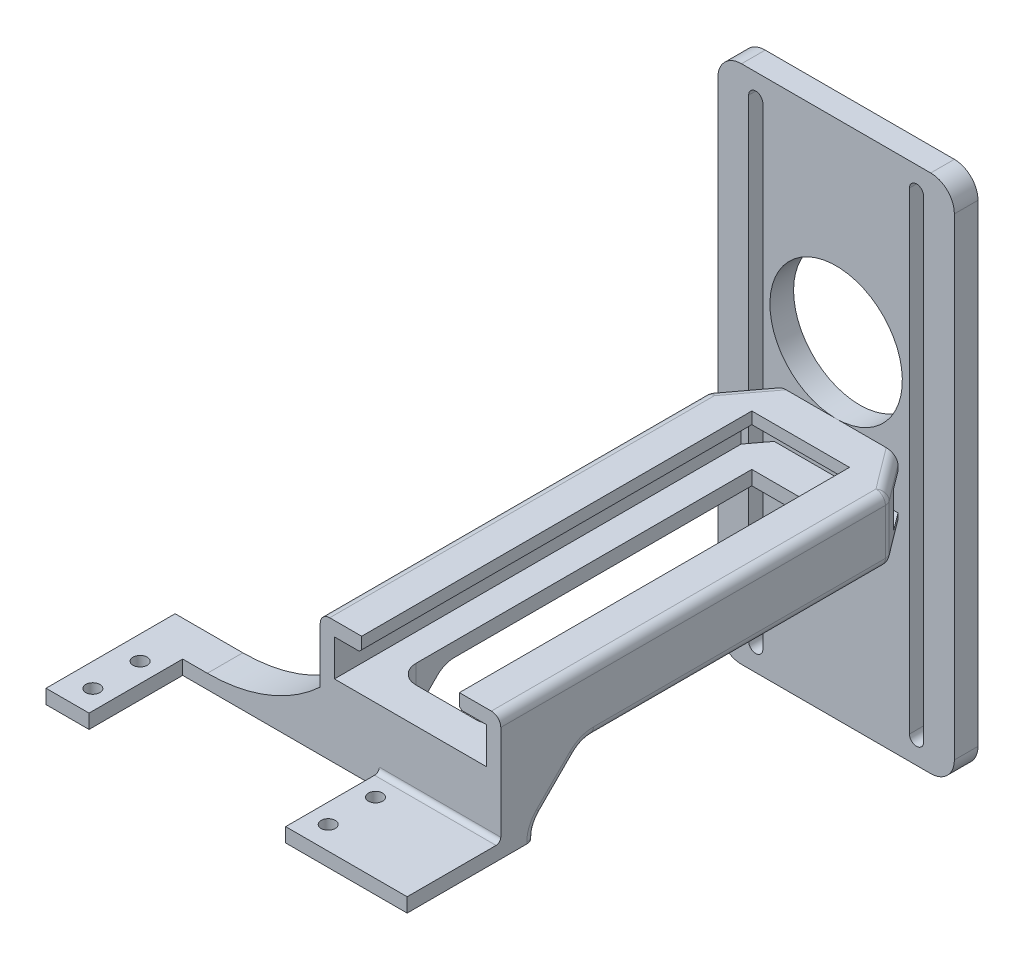
SolidWorks part; units mm, degrees
ref_plane "Front Plane" through (0, 0, 0) normal (0, 0, 1) x (1, 0, 0)
ref_plane "Top Plane" through (0, 0, 0) normal (0, 1, 0) x (1, 0, 0)
ref_plane "Right Plane" through (0, 0, 0) normal (1, 0, 0) x (0, 0, -1)
sketch "Sketch1" plane through (0, 0, 0) normal (0, 0, 1) x (1, 0, 0)
  line L0 (-69.7691, 23.4512) -> (-75.5286, 23.4512)
  line L1 (-75.5286, 23.4512) -> (-75.5286, 15.7512)
  line L2 (-75.5286, 15.7512) -> (-69.7691, 15.7512)
  line L3 (-69.7691, 15.7512) -> (-69.7691, 12.7512)
  line L4 (-69.7691, 12.7512) -> (-78.5286, 12.7512)
  line L5 (-78.5286, 12.7512) -> (-78.5286, 26.4512)
  line L6 (-78.5286, 26.4512) -> (-69.7691, 26.4512)
  line L7 (-69.7691, 26.4512) -> (-69.7691, 23.4512)
  line L8 (-49.1122, 23.4512) -> (-49.1122, 26.4512)
  line L9 (-49.1122, 26.4512) -> (-40.3527, 26.4512)
  line L10 (-40.3527, 26.4512) -> (-40.3527, 12.7512)
  line L11 (-40.3527, 12.7512) -> (-49.1122, 12.7512)
  line L12 (-49.1122, 12.7512) -> (-49.1122, 15.7512)
  line L13 (-49.1122, 15.7512) -> (-43.3527, 15.7512)
  line L14 (-43.3527, 15.7512) -> (-43.3527, 23.4512)
  line L15 (-43.3527, 23.4512) -> (-49.1122, 23.4512)
  dimension "D2" = 5.7594
  dimension "D8" = 3
  dimension "D9" = 3
extrude "Boss-Extrude1" add sketch "Sketch1" along normal blind 55 and the other way blind 35
sketch "Sketch2" plane through (0, 26.4512, 0) normal (0, 1, 0) x (1, 0, 0)
  line L0 (-40.3527, 35) -> (-40.3527, -55) construction
  line L6 (-78.5286, 35) -> (-40.3527, 35)
  line L7 (-78.5286, 35) -> (-78.5286, 27.5)
  line L8 (-78.5286, 27.5) -> (-40.3527, 27.5)
  line L9 (-40.3527, 35) -> (-40.3527, 27.5)
  dimension "D1" = 7.5
extrude "Boss-Extrude2" add sketch "Sketch2" against normal up to vertex (3 mm away) up to point (-69.7691, 23.4512, -35)
sketch "Sketch3" plane through (0, 12.7512, 0) normal (0, -1, 0) x (1, 0, 0)
  line L0 (-40.3527, -35) -> (-40.3527, 55) construction
  line L1 (-78.5286, 55) -> (-40.3527, 55)
  line L2 (-78.5286, 55) -> (-78.5286, 47.5)
  line L3 (-78.5286, 47.5) -> (-40.3527, 47.5)
  line L4 (-40.3527, 55) -> (-40.3527, 47.5)
  line L6 (-78.5286, -35) -> (-40.3527, -35)
  line L7 (-78.5286, -35) -> (-78.5286, -27.5)
  line L8 (-78.5286, -27.5) -> (-40.3527, -27.5)
  line L9 (-40.3527, -35) -> (-40.3527, -27.5)
  line L10 (-69.7691, -27.5) -> (-49.1122, -27.5) construction
extrude "Boss-Extrude3" add sketch "Sketch3" against normal up to vertex (3 mm away) up to point (-69.7691, 15.7512, 55)
ref_plane "MidSlide" through (0, 19.6012, 0) normal (0, 1, 0) x (1, 0, 0)
ref_plane "Plane2" through (-59.4407, 0, 0) normal (1, 0, 0) x (0, 0, -1)
sketch "Sketch4" plane through (0, 3.3512, 0) normal (0, -1, 0) x (1, 0, 0)
  line L0 (-69.7691, 47.5) -> (-49.1122, 47.5) construction
  line L1 (-116.7182, 74.8) -> (-116.7182, 47.5)
  line L2 (-116.7182, 47.5) -> (-40.3527, 47.5)
  line L3 (-40.3527, -35) -> (-40.3527, 55) construction
  line L4 (-40.3527, 47.5) -> (-40.3527, 55)
  line L5 (-113.1286, 73.8) -> (-107.1286, 73.8) construction
  line L6 (-116.7182, 74.8) -> (-107.6165, 74.8)
  line L7 (-107.6165, 74.8) -> (-107.6165, 55)
  line L8 (-40.3527, 55) -> (-107.6165, 55) construction
  line L9 (-107.1165, 73.8) -> (-107.1165, 56) construction
  line L11 (-78.5286, 55) -> (-40.3527, 55) construction
  line L12 (-107.6165, 55) -> (-66.0407, 55)
  line L13 (-66.0407, 55) -> (-66.0407, 74.8)
  line L14 (-66.0407, 74.8) -> (-40.3527, 74.8)
  line L15 (-40.3527, 74.8) -> (-40.3527, 55)
  line L16 (-66.5407, 56) -> (-66.5407, 73.8) construction
  arc A0 (-113.5286, 68.65) -> (-113.5286, 71.15) centre (-111.7182, 69.9) ccw construction
  circle A1 centre (-111.7182, 69.9) radius 1.5
  circle A2 centre (-111.7182, 59.9) radius 1.5
  circle A3 centre (-61.939, 69.9) radius 1.5
  circle A4 centre (-61.939, 59.9) radius 1.5
  circle A5 centre (-64.4407, 35.969) radius 1.5 construction
  dimension "D1" = 5
  dimension "D2" = 1
  dimension "D3" = 0.5
  dimension "D4" = 0.5
extrude "Boss-Extrude4" add sketch "Sketch4" along normal blind 3 separate body
sketch "Sketch5" plane through (0, 12.7512, 0) normal (0, -1, 0) x (1, 0, 0)
  line L0 (-116.7182, 47.5) -> (-40.3527, 47.5) construction
  line L1 (-78.5355, 47.5) -> (-40.3527, 47.5)
  line L2 (-78.5355, 47.5) -> (-78.5355, 55)
  line L3 (-78.5355, 55) -> (-40.3527, 55)
  line L4 (-40.3527, 47.5) -> (-40.3527, 55)
  line L5 (-40.3527, 47.5) -> (-40.3527, 74.8) construction
extrude "Boss-Extrude5" add sketch "Sketch5" along normal up to next
fillet "Fillet1" radius 35 1 edges
sketch "Sketch6" plane through (0, 0, -35) normal (0, 0, -1) x (-1, 0, 0)
  line L0 (75.5286, 23.4512) -> (43.3527, 23.4512) construction
  line L1 (34.4407, 81.4512) -> (84.4407, 81.4512)
  line L2 (34.4407, 81.4512) -> (34.4407, -28.5488)
  line L3 (34.4407, -28.5488) -> (84.4407, -28.5488)
  line L4 (84.4407, 81.4512) -> (84.4407, -28.5488)
  line L8 (76.4407, 76.4512) -> (76.4407, -23.5488) construction
  line L12 (77.9407, 76.4512) -> (77.9407, -23.5488)
  line L13 (74.9407, 76.4512) -> (74.9407, -23.5488)
  line L14 (42.4407, 76.4512) -> (42.4407, -23.5488) construction
  line L15 (43.9407, 76.4512) -> (43.9407, -23.5488)
  line L16 (40.9407, 76.4512) -> (40.9407, -23.5488)
  line L18 (69.7691, 26.4512) -> (78.5286, 26.4512) construction
  circle A4 centre (59.4407, 40.4512) radius 14
  arc A5 (77.9407, 76.4512) -> (74.9407, 76.4512) centre (76.4407, 76.4512) ccw
  arc A6 (74.9407, -23.5488) -> (77.9407, -23.5488) centre (76.4407, -23.5488) ccw
  arc A7 (43.9407, 76.4512) -> (40.9407, 76.4512) centre (42.4407, 76.4512) ccw
  arc A8 (40.9407, -23.5488) -> (43.9407, -23.5488) centre (42.4407, -23.5488) ccw
  point P6 (59.4407, 81.4512)
  point P9 (59.4407, 23.4512)
  point P11 (34.4407, 26.4512)
  point P13 (76.4407, 26.4512)
  point P31 (42.4407, 26.4512)
  dimension "D3" = 14
  dimension "D5" = 28
  dimension "D6" = 17
  dimension "D4" = 5
  dimension "D11" = 100
  dimension "D2" = 5
  dimension "D7" = 110
  dimension "D8" = 50
  dimension "D9" = 17
  dimension "D10" = 36
  dimension "D12" = 3
extrude "Base" add sketch "Sketch6" along normal blind 5
fillet "Fillet4" radius 1 1 edges
chamfer "Chamfer1" distance 0.5 angle 45 3 edges at (-69.7691, 23.4512, 13.75) (-49.1122, 23.4512, 13.75) (-59.4407, 23.4512, -27.5)
chamfer "Chamfer2" distance 10 angle 45 2 edges
fillet "Fillet7" radius 5 4 edges at (-44.7324, 2.7512, 47.5) (-74.1489, 2.7512, 47.5) (-44.7324, 12.7512, 37.5) (-74.1489, 12.7512, 37.5)
ref_plane "Plane3" through (-40.3527, 26.4512, -35) normal (0, 0, -1) x (-1, 0, 0)
sketch "Sketch12" plane through (0, 26.4512, 0) normal (0, 1, 0) x (1, 0, 0)
  line L0 (-46.3527, 35) -> (-40.3527, 35)
  line L1 (6.6981, 35) -> (-157.857, 35) construction
  line L2 (-40.3527, 35) -> (-40.3527, 27)
  line L3 (-40.3527, -55) -> (-40.3527, 35) construction
  line L4 (-40.3527, 27) -> (-46.3527, 35)
extrude "Cut-Extrude2" cut sketch "Sketch12" against normal blind 15 contours L4 L0 L2
fillet "Fillet9" radius 2 1 edges at (-40.3527, 19.6012, -27)
sketch "Sketch13" plane through (0, 26.4512, 0) normal (0, 1, 0) x (1, 0, 0)
  line L0 (-78.5286, 35) -> (-78.5286, 27)
  line L1 (-78.5286, 35) -> (-78.5286, -55) construction
  line L2 (-78.5286, 27) -> (-72.5286, 35)
  line L3 (-46.3527, 35) -> (-59.4407, 35) construction
  line L4 (-72.5286, 35) -> (-78.5286, 35)
extrude "Cut-Extrude3" cut sketch "Sketch13" against normal blind 14
fillet "Fillet16" radius 2 1 edges at (-78.5286, 19.6012, -27)
fillet "Fillet18" radius 5 4 edges at (-84.4407, -28.5488, -37.5) (-34.4407, -28.5488, -37.5) (-34.4407, 81.4512, -37.5) (-84.4407, 81.4512, -37.5)
fillet "Fillet38" radius 2 19 edges at (-43.5527, 12.7512, -31.2667) (-40.4554, 12.7512, -26.9658) (-40.3527, 2.5935, 47.1194) (-40.3527, 7.7512, 42.5) (-40.3527, 12.3706, 37.3423) (-75.3286, 26.4512, -31.2667) (-78.426, 26.4512, -26.9658) (-43.5527, 26.4512, -31.2667) (-40.4554, 26.4512, -26.9658) (-78.5286, 26.4512, 14.3333) (-40.3527, 26.4512, 14.3333) (-75.3286, 12.7512, -31.2667) (-78.426, 12.7512, -26.9658) (-78.5286, 2.5935, 47.1194) (-78.5286, 7.7512, 42.5) (-78.5286, 12.3706, 37.3423) (-78.5286, 12.7512, 4.5478)
fillet "Fillet40" radius 4 4 edges at (-78.2626, 4.0028, 47.5) (-78.5286, 9.1651, 47.5)
